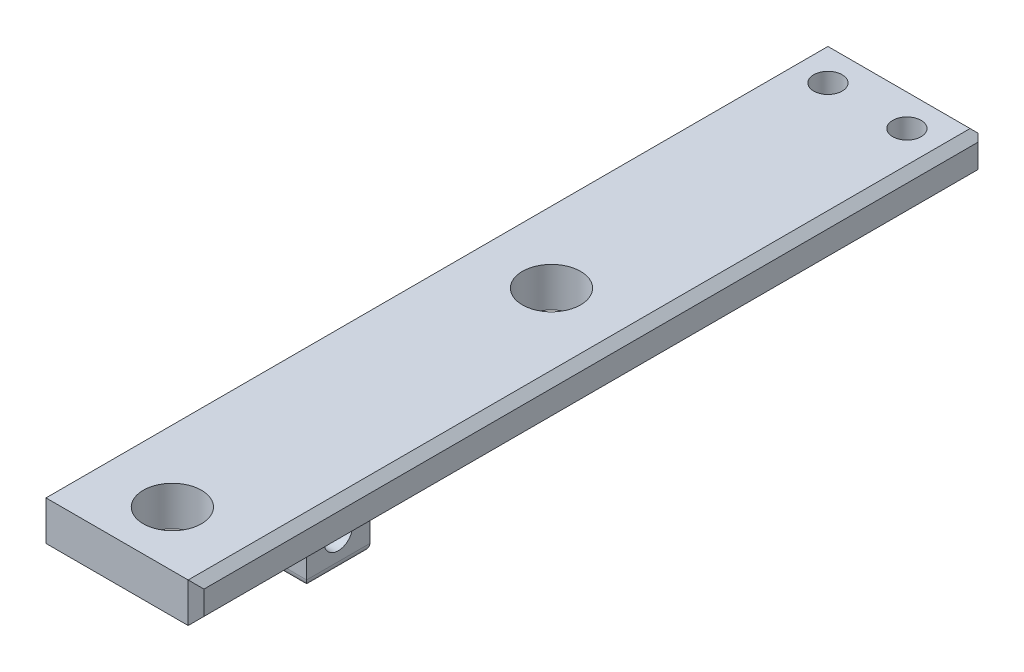
SolidWorks part; units mm, degrees
ref_plane "Front Plane" through (0, 0, 0) normal (0, 0, 1) x (1, 0, 0)
ref_plane "Top Plane" through (0, 0, 0) normal (0, 1, 0) x (1, 0, 0)
ref_plane "Right Plane" through (0, 0, 0) normal (1, 0, 0) x (0, 0, -1)
sketch "Sketch1" plane through (0, 0, 0) normal (0, 1, 0) x (1, 0, 0)
  line L1 (0, 0) -> (20, 0)
  line L2 (0, 0) -> (0, 100)
  line L3 (0, 100) -> (20, 100)
  line L4 (20, 0) -> (20, 100)
  dimension "D1" = 20
  dimension "D2" = 100
extrude "Boss-Extrude1" add sketch "Sketch1" along normal blind 5
hole_wizard "M3 Clearance Hole1" positions "3DSketch1" profile "Sketch2" hole size "M3" standard "ANSI Metric" end condition through all
sketch3d "3DSketch1"
  line L0 (20, 0, -100) -> (0, 0, -100) construction
  line L1 (20, 0, 0) -> (20, 0, -100) construction
  point P0 (15, 0, -95)
  dimension "D1" = 5
  dimension "D2" = 5
sketch "Sketch2" plane through (15, 0, -95) normal (1, 0, 0) x (0, 0, -1)
  line L0 (0, 0) -> (0, 5)
  line L1 (0, 5) -> (1.8, 5)
  line L2 (1.8, 5) -> (1.8, 0)
  line L5 (1.8, 0) -> (0, 0)
  line L11 (0, -6.35) -> (0, 107.95) construction
  dimension "Thru Hole Dia." = 3.6
  dimension "Thru Hole Depth" = 5
sketch "Sketch3" plane through (0, 0, 0) normal (0, -1, 0) x (1, 0, 0)
  line L0 (0, -100) -> (0, 0) construction
  line L1 (6, -20) -> (14, -20)
  line L2 (6, -20) -> (6, -28)
  line L3 (6, -28) -> (14, -28)
  line L4 (14, -20) -> (14, -28)
  line L5 (0, 0) -> (20, 0) construction
  dimension "D1" = 8
  dimension "D2" = 6
  dimension "D3" = 20
  dimension "D4" = 8
extrude "Boss-Extrude2" add sketch "Sketch3" along normal blind 8.5
hole_wizard "M3 Clearance Hole5" positions "3DSketch5" profile "Sketch7" hole size "M3" standard "ANSI Metric" end condition through all
sketch3d "3DSketch5"
  line L0 (6, -8.5, -20) -> (6, -8.5, -28) construction
  line L1 (6, -8.5, -28) -> (6, 0, -28) construction
  point P0 (6, -4.5, -24)
  dimension "D1" = 4
  dimension "D2" = 4
sketch "Sketch7" plane through (6, -4.5, -24) normal (0, 1, 0) x (0, 0, 1)
  line L0 (0, 0) -> (0, 14)
  line L1 (0, 14) -> (1.8, 14)
  line L2 (1.8, 14) -> (1.8, 0)
  line L5 (1.8, 0) -> (0, 0)
  line L11 (0, -6.35) -> (0, 107.95) construction
  dimension "Thru Hole Dia." = 3.6
  dimension "Thru Hole Depth" = 14
hole_wizard "E (0.29) Diameter Hole2" positions "3DSketch6" profile "Sketch8" hole size "E" standard "ANSI Inch" end condition through all
sketch3d "3DSketch6"
  line L0 (20, 0, -100) -> (0, 0, -100) construction
  line L1 (20, 0, 0) -> (20, 0, -100) construction
  point P0 (10, 0, -55)
  dimension "D1" = 45
  dimension "D2" = 10
sketch "Sketch8" plane through (10, 0, -55) normal (1, 0, 0) x (0, 0, -1)
  line L0 (0, 0) -> (0, 5)
  line L1 (0, 5) -> (3.683, 5)
  line L2 (3.683, 5) -> (3.683, 0)
  line L5 (3.683, 0) -> (0, 0)
  line L11 (0, -6.35) -> (0, 107.95) construction
  dimension "Thru Hole Dia." = 7.366
  dimension "Thru Hole Depth" = 5
chamfer "Chamfer1" distance 1 angle 45 8 edges at (20, 2.5, -100) (20, 0, -50) (20, 5, -50) (0, 0, -50) (0, 2.5, -100) (0, 5, -50) (20, 2.5, 0) (0, 2.5, 0)
hole_wizard "E (0.29) Diameter Hole1" positions "3DSketch8" profile "Sketch10" hole size "E" standard "ANSI Inch" end condition through all
sketch3d "3DSketch8"
  line L0 (19, 0, -100) -> (19, 0, 0) construction
  line L1 (1, 0, 0) -> (19, 0, 0) construction
  point P0 (10, 0, -7)
  dimension "D1" = 9
  dimension "D2" = 7
sketch "Sketch10" plane through (10, 0, -7) normal (1, 0, 0) x (0, 0, -1)
  line L0 (0, 0) -> (0, 5)
  line L1 (0, 5) -> (3.683, 5)
  line L2 (3.683, 5) -> (3.683, 0)
  line L5 (3.683, 0) -> (0, 0)
  line L11 (0, -6.35) -> (0, 107.95) construction
  dimension "Thru Hole Dia." = 7.366
  dimension "Thru Hole Depth" = 5
fillet "Fillet3" radius 1 4 edges at (10, -8.5, -28) (6, -8.5, -24) (10, -8.5, -20) (14, -8.5, -24)
chamfer "Chamfer2" distance 1 angle 45 2 edges at (10, 5, -100) (10, 0, -100)
hole_wizard "M3 Clearance Hole6" positions "3DSketch10" profile "Sketch12" hole size "M3" standard "ANSI Metric" end condition through all
sketch3d "3DSketch10"
  line L0 (1, 0, -99) -> (19, 0, -99) construction
  line L1 (1, 0, 0) -> (1, 0, -99) construction
  point P0 (5, 0, -95)
  dimension "D1" = 4
  dimension "D2" = 4
sketch "Sketch12" plane through (5, 0, -95) normal (1, 0, 0) x (0, 0, -1)
  line L0 (0, 0) -> (0, 5)
  line L1 (0, 5) -> (1.8, 5)
  line L2 (1.8, 5) -> (1.8, 0)
  line L5 (1.8, 0) -> (0, 0)
  line L11 (0, -6.35) -> (0, 107.95) construction
  dimension "Thru Hole Dia." = 3.6
  dimension "Thru Hole Depth" = 5
